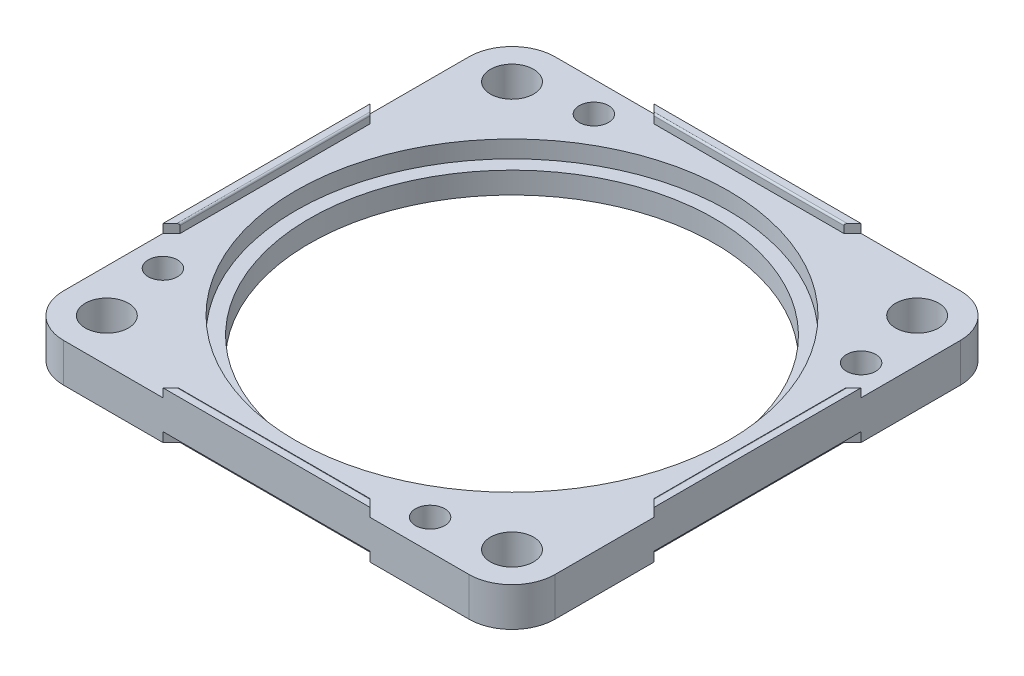
SolidWorks part; units mm, degrees
ref_plane "Front Plane" through (0, 0, 0) normal (0, 0, 1) x (1, 0, 0)
ref_plane "Top Plane" through (0, 0, 0) normal (0, 1, 0) x (1, 0, 0)
ref_plane "Right Plane" through (0, 0, 0) normal (1, 0, 0) x (0, 0, -1)
sketch "Sketch1" plane through (0, 0, 0) normal (0, 1, 0) x (1, 0, 0)
  line L1 (28.5, -28.5) -> (-28.5, -28.5)
  line L2 (28.5, -28.5) -> (28.5, 28.5)
  line L3 (28.5, 28.5) -> (-28.5, 28.5)
  line L4 (-28.5, -28.5) -> (-28.5, 28.5)
  line L5 (28.5, -28.5) -> (-28.5, 28.5) construction
  line L6 (28.5, 28.5) -> (-28.5, -28.5) construction
  point P0 (0, 0)
  dimension "D1" = 57
extrude "Boss-Extrude1" add sketch "Sketch1" along normal blind 4.5
fillet "Fillet1" radius 5 4 edges at (-28.5, 2.25, -28.5) (28.5, 2.25, -28.5) (-28.5, 2.25, 28.5) (28.5, 2.25, 28.5)
sketch "Sketch2" plane through (0, 4.5, 0) normal (0, 1, 0) x (1, 0, 0)
  line L0 (0, 0) -> (39.5802, 0) construction
  line L1 (0, 0) -> (0, 12.5817) construction
  line L2 (23.5, 28.5) -> (-23.5, 28.5) construction
  line L7 (23.5, 28.5) -> (-23.5, 28.5)
  line L8 (-28.5, 23.5) -> (-28.5, -23.5)
  line L9 (-23.5, -28.5) -> (23.5, -28.5)
  line L10 (28.5, -23.5) -> (28.5, 23.5)
  line L11 (23.5, 28.5) -> (-23.5, 28.5)
  line L12 (-28.5, 23.5) -> (-28.5, -23.5)
  line L13 (-23.5, -28.5) -> (23.5, -28.5)
  line L14 (28.5, -23.5) -> (28.5, 23.5)
  circle A0 centre (-23.5, 23.5) radius 2.5
  circle A1 centre (-15.5, 25) radius 1.7
  arc A6 (-23.5, 28.5) -> (-28.5, 23.5) centre (-23.5, 23.5) ccw
  arc A7 (-28.5, -23.5) -> (-23.5, -28.5) centre (-23.5, -23.5) ccw
  arc A8 (23.5, -28.5) -> (28.5, -23.5) centre (23.5, -23.5) ccw
  arc A9 (28.5, 23.5) -> (23.5, 28.5) centre (23.5, 23.5) ccw
  arc A10 (-23.5, 28.5) -> (-28.5, 23.5) centre (-23.5, 23.5) ccw
  arc A11 (-28.5, -23.5) -> (-23.5, -28.5) centre (-23.5, -23.5) ccw
  arc A12 (23.5, -28.5) -> (28.5, -23.5) centre (23.5, -23.5) ccw
  arc A13 (28.5, 23.5) -> (23.5, 28.5) centre (23.5, 23.5) ccw
  dimension "D1" = 5
  dimension "D2" = 3.4
  dimension "D3" = 3.5
  dimension "D5" = 8
  dimension "D4" = 0
extrude "Cut-Extrude1" cut sketch "Sketch2" against normal through all contours A0 | A1
sketch "Sketch3" plane through (0, 4.5, 0) normal (0, 1, 0) x (1, 0, 0)
  line L0 (0, 0) -> (0, 41.0184) construction
  line L1 (11, 27.5) -> (-11, 27.5)
  line L2 (-11, 27.5) -> (-12, 28.5)
  line L3 (23.5, 28.5) -> (-23.5, 28.5) construction
  line L4 (11, 27.5) -> (12, 28.5)
  line L5 (-12, 28.5) -> (12, 28.5)
  point P9 (0, 27.5)
  dimension "D1" = 1
  dimension "D2" = 135
  dimension "D3" = 11
extrude "Boss-Extrude2" add sketch "Sketch3" along normal blind 1
fillet "Fillet2" radius 0.2 1 edges at (0, 5.5, -27.5)
sketch "Sketch4" plane through (0, 4.5, 0) normal (0, 1, 0) x (1, 0, 0)
  circle A0 centre (0, 0) radius 23.5
  circle A1 centre (0, 0) radius 25.1
  dimension "D1" = 47
  dimension "D2" = 50.2
extrude "Cut-Extrude2" cut sketch "Sketch4" against normal through all contours A0
extrude "Cut-Extrude3" cut sketch "Sketch4<3>" against normal blind 2
sketch "Sketch4<3>" plane through (0, 4.5, 0) normal (0, 1, 0) x (1, 0, 0) same geometry as "Sketch4"
sketch "Sketch5" plane through (0, 0, 0) normal (0, -1, 0) x (1, 0, 0)
  line L0 (0, 0) -> (0, -40.5062) construction
  line L1 (-11, -27.5) -> (11, -27.5)
  line L2 (11, -27.5) -> (12, -28.5)
  line L3 (23.5, -28.5) -> (-23.5, -28.5) construction
  line L4 (-11, -27.5) -> (-12, -28.5)
  line L5 (-12, -28.5) -> (12, -28.5)
  point P10 (0, -27.5)
  dimension "D1" = 135
  dimension "D2" = 11
  dimension "D3" = 1
extrude "Cut-Extrude4" cut sketch "Sketch5" against normal blind 1.1
pattern_circular "CirPattern1" count 4 over 360 about axis through (0, 2.5, 0) along (0, 1, 0) of "Cut-Extrude4", "Fillet2", "Boss-Extrude2", "Cut-Extrude1"
